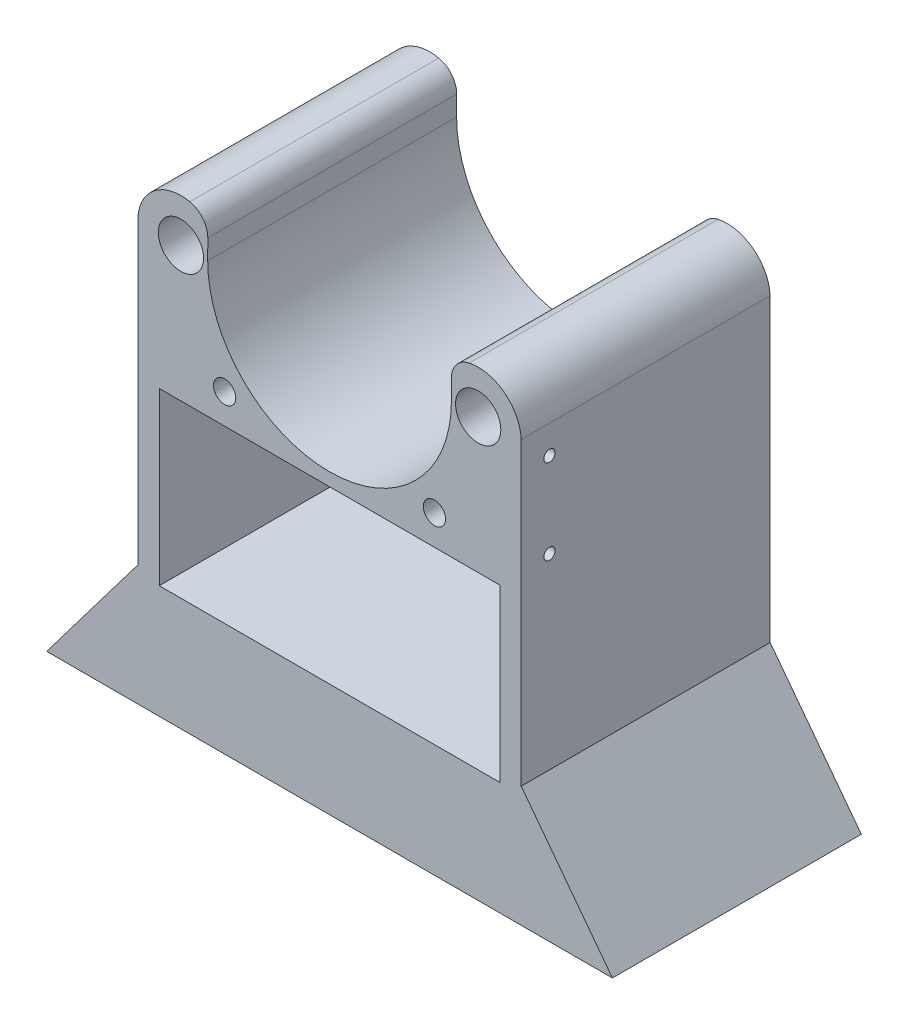
SolidWorks part; units mm, degrees
ref_plane "Front Plane" through (0, 0, 0) normal (0, 0, 1) x (1, 0, 0)
ref_plane "Top Plane" through (0, 0, 0) normal (0, 1, 0) x (1, 0, 0)
ref_plane "Right Plane" through (0, 0, 0) normal (1, 0, 0) x (0, 0, -1)
sketch "Sketch1" plane through (0, 0, 0) normal (0, 0, 1) x (1, 0, 0)
  line L0 (0, 0) -> (0, 54.0315) construction
  line L1 (-38.227, -19.177) -> (38.227, -19.177)
  line L2 (-38.227, -19.177) -> (-38.227, 19.177)
  line L3 (-38.227, 19.177) -> (38.227, 19.177)
  line L4 (38.227, -19.177) -> (38.227, 19.177)
  line L5 (-38.227, -19.177) -> (38.227, 19.177) construction
  line L6 (-38.227, 19.177) -> (38.227, -19.177) construction
  line L7 (0, 54.0315) -> (0, -50.3288) construction
  line L8 (-38.227, 7.4711) -> (-38.227, 58.2157) construction
  line L9 (-43.03, -17.5223) -> (-43.03, 19.177)
  line L10 (-63.5, -44.577) -> (63.5, -44.577)
  line L11 (-43.03, -17.5223) -> (-63.5, -44.577)
  line L12 (-43.03, -17.5223) -> (-43.03, 56.2622) construction
  line L13 (-43.03, 19.177) -> (-43.03, 49.8911)
  line L14 (-23.6995, 49.9018) -> (0, 24.257)
  line L15 (43.03, -17.5223) -> (63.5, -44.577)
  line L16 (43.03, 19.177) -> (43.03, 49.8911)
  line L17 (43.03, -17.5223) -> (43.03, 19.177)
  line L18 (23.6995, 49.9018) -> (0, 24.257)
  circle A0 centre (-33.3645, 49.4395) radius 4.8625
  circle A1 centre (33.3645, 49.4395) radius 4.8625
  arc A2 (-43.03, 49.8911) -> (-23.6995, 49.9018) centre (-33.3645, 49.4395) cw
  arc A3 (43.03, 49.8911) -> (23.6995, 49.9018) centre (33.3645, 49.4395) ccw
  point P0 (0, 0)
  point P11 (-33.3645, 44.577)
  point P14 (-38.227, 49.4395)
  point P24 (0, 24.257)
  dimension "D3" = 9.725
  dimension "D1" = 76.454
  dimension "D2" = 38.354
  dimension "D4" = 0
  dimension "D5" = 25.4
  dimension "D6" = 5.08
  dimension "D7" = 63.5
  dimension "D9" = 25.4
  dimension "D10" = 5.08
extrude "Boss-Extrude1" add sketch "Sketch1" along normal blind 50.8
sketch "Sketch2" plane through (0, 0, 0) normal (0, 0, -1) x (-1, 0, 0)
  line L0 (-43.03, 49.8911) -> (-43.03, -17.5223)
  line L1 (-43.03, -17.5223) -> (-63.5, -44.577)
  line L2 (-63.5, -44.577) -> (63.5, -44.577)
  line L3 (63.5, -44.577) -> (43.03, -17.5223)
  line L4 (43.03, -17.5223) -> (43.03, 49.8911)
  line L5 (23.6995, 49.9018) -> (0, 24.257)
  line L6 (0, 24.257) -> (-23.6995, 49.9018)
  arc A0 (-43.03, 49.8911) -> (-23.6995, 49.9018) centre (-33.3648, 49.8911) cw
  arc A1 (23.6995, 49.9018) -> (43.03, 49.8911) centre (33.3648, 49.8911) cw
extrude "Boss-Extrude2" add sketch "Sketch2" along normal blind 5.08
sketch "Sketch3" plane through (0, 0, -5.08) normal (0, 0, -1) x (-1, 0, 0)
  line L0 (-33.3701, 59.5563) -> (33.3701, 59.5563)
  line L1 (-23.6995, 49.9018) -> (0, 24.257)
  line L2 (0, 24.257) -> (23.6995, 49.9018)
  arc A0 (-23.6995, 49.9018) -> (-43.03, 49.8911) centre (-33.3648, 49.8911) ccw construction
  arc A1 (43.03, 49.8911) -> (23.6995, 49.9018) centre (33.3648, 49.8911) ccw construction
  arc A2 (-33.3701, 59.5563) -> (-23.6995, 49.9018) centre (-33.3701, 49.8857) cw
  arc A3 (23.6995, 49.9018) -> (33.3701, 59.5563) centre (33.3701, 49.8857) cw
extrude "Boss-Extrude3" add sketch "Sketch3" against normal up to surface (55.88 mm away) up to face at (-28.502, 49.4395, 50.8)
sketch "Sketch5" plane through (0, 0, 50.8) normal (0, 0, 1) x (1, 0, 0)
  line L0 (-33.3645, 49.4395) -> (33.3645, 49.4395) construction
  point P4 (0, 49.4395)
ref_axis "Axis1" through (0, 49.4395, 50.8) along (0, 0, -1)
sketch "Sketch6" plane through (0, 0, 50.8) normal (0, 0, 1) x (1, 0, 0)
  line L0 (-24.765, 49.4395) -> (-24.765, 59.5563)
  line L1 (-33.3701, 59.5563) -> (33.3701, 59.5563) construction
  line L2 (24.765, 49.4395) -> (24.765, 59.5563)
  line L3 (-24.765, 59.5563) -> (24.765, 59.5563)
  circle A0 centre (0, 49.4395) radius 24.765
  arc M6 (43.03, 49.8911) -> (23.6995, 49.9018) centre (33.3645, 49.4395) ccw
  arc M7 (23.6995, 49.9018) -> (33.3701, 59.5563) centre (33.3701, 49.8857) cw
  line M8 (33.3701, 59.5563) -> (-33.3701, 59.5563)
  arc M9 (-33.3701, 59.5563) -> (-23.6995, 49.9018) centre (-33.3701, 49.8857) cw
  arc M10 (-23.6995, 49.9018) -> (-43.03, 49.8911) centre (-33.3645, 49.4395) ccw
  dimension "D1" = 49.53
extrude "Cut-Extrude1" cut sketch "Sketch6" against normal blind 157.734 contours A0 L3 M7 M9 M10 M6 | A0 L0 M8 M9 | A0 L2 M7 M8 region at (0, 44.1265, 50.8) region at (-24.0725, 57.4402, 50.8) region at (24.0725, 57.4402, 50.8)
fillet "Fillet1" radius 2.54 2 edges at (24.765, 59.5563, 22.86) (-24.765, 59.5563, 22.86)
sketch "Sketch7" plane through (0, 0, -5.08) normal (0, 0, -1) x (-1, 0, 0)
  circle A0 centre (-23.55, 25.8895) radius 2.5
  circle A1 centre (23.55, 25.8895) radius 2.5
extrude "Cut-Extrude2" cut sketch "Sketch7" against normal blind 157.734
sketch "Sketch8" plane through (0, 0, 0) normal (0, 0, 1) x (1, 0, 0)
  circle A1 centre (18.8761, 0.1739) radius 3.3274
  circle A2 centre (-19.2239, 0.1739) radius 3.3274
extrude "Cut-Extrude3" cut sketch "Sketch8" against normal blind 50.8
sketch "Sketch9" plane through (0, 0, 50.8) normal (0, 0, 1) x (1, 0, 0)
  circle A0 centre (-33.3645, 49.4395) radius 5.08
  circle A1 centre (33.3645, 49.4395) radius 5.08
  dimension "D1" = 10.16
  dimension "D2" = 10.16
extrude "Cut-Extrude4" cut sketch "Sketch9" against normal up to surface (50.8 mm away) up to face at (-28.502, 49.4395, 0)
sketch "Sketch10" plane through (-43.03, 0, 0) normal (-1, 0, 0) x (0, 0, 1)
  line L0 (44.45, 49.8911) -> (44.45, -17.5223) construction
  line L1 (50.8, 49.8911) -> (0, 49.8911) construction
  line L2 (50.8, -17.5223) -> (-5.08, -17.5223) construction
  line L3 (50.8, 49.8911) -> (50.8, -17.5223) construction
  circle A0 centre (44.45, 43.5411) radius 1.27
  circle A1 centre (44.45, 24.4911) radius 1.27
  dimension "D2" = 2.54
  dimension "D3" = 2.54
  dimension "D4" = 6.35
  dimension "D5" = 19.05
  dimension "D1" = 6.35
extrude "Cut-Extrude5" cut sketch "Sketch10" against normal blind 6.35
sketch "Sketch11" plane through (0, 0, -5.08) normal (0, 0, -1) x (-1, 0, 0)
  line L0 (27.3504, 49.4395) -> (27.305, 59.5563)
  line L1 (-27.3504, 49.4395) -> (-27.305, 59.5563)
  circle A0 centre (0, 49.4395) radius 27.3504
  arc A1 (-27.305, 59.5563) -> (-25.5089, 58.8124) centre (-27.305, 57.0163) cw
  arc A2 (-24.765, 57.0163) -> (-27.305, 59.5563) centre (-27.305, 57.0163) ccw construction
  arc A3 (27.305, 59.5563) -> (25.5089, 58.8124) centre (27.305, 57.0163) ccw
  arc A4 (27.305, 59.5563) -> (24.765, 57.0163) centre (27.305, 57.0163) ccw construction
  line M6 (-24.765, 54.2984) -> (-24.765, 57.0163)
  arc M7 (-24.765, 57.0163) -> (-27.305, 59.5563) centre (-27.305, 57.0163) ccw
  arc M17 (27.305, 59.5563) -> (24.765, 57.0163) centre (27.305, 57.0163) ccw
  line M18 (24.765, 57.0163) -> (24.765, 54.2984)
  arc M19 (24.765, 54.2984) -> (23.6995, 49.9018) centre (33.3701, 49.8857) ccw
  arc M20 (23.6995, 49.9018) -> (24.4702, 53.2495) centre (33.3645, 49.4395) cw
  arc M21 (24.4702, 53.2495) -> (-24.4702, 53.2495) centre (0, 49.4395) cw
  arc M22 (-24.4702, 53.2495) -> (-23.6995, 49.9018) centre (-33.3645, 49.4395) cw
  arc M23 (-23.6995, 49.9018) -> (-24.765, 54.2984) centre (-33.3701, 49.8857) ccw
  dimension "D1" = 10.1168
extrude "Cut-Extrude8" cut sketch "Sketch11" against normal blind 60.198 contours A0 M17 M7 M6 M23 M22 M21 M20 M19 M18 | L0 A0 L1 M17 M18 M19 M20 M21 M22 M23 M6 M7 | A0 L1 M7 | A0 L0 M17 region at (0, 22.7487, -5.08) region at (-26.8047, 56.9219, -5.08) region at (0, 51.0402, -5.08) region at (26.8047, 56.9219, -5.08)
sketch "Sketch13" plane through (0, 0, 50.8) normal (0, 0, 1) x (1, 0, 0)
  line L0 (-43.0405, 49.4395) -> (-48.2287, 49.4395)
  line L1 (-27.3165, 56.9924) -> (-24.2675, 60.915)
  circle A0 centre (-33.3645, 49.4395) radius 9.676
  circle A1 centre (-33.3645, 49.4395) radius 14.8642
  arc M2 (-27.3165, 56.9924) -> (-43.03, 49.8911) centre (-33.3645, 49.4395) ccw
  arc M10 (27.3504, 49.4395) -> (-27.3504, 49.4395) centre (0, 49.4395) cw
extrude "Cut-Extrude10" cut sketch "Sketch13" against normal blind 134.112 contours A1 L0 A0 M10 M2 region at (-45.6346, 49.8401, 50.8)
ref_plane "Plane1" through (0, 0, 0) normal (-1, 0, 0) x (0, 0, 1)
mirror "Mirror1" about plane through (0, 0, 0) normal (-1, 0, 0) of "Cut-Extrude10"
mirror "Mirror2" about plane through (0, 0, 0) normal (-1, 0, 0) of "Cut-Extrude5"
fillet "Fillet2" radius 5.08 2 edges at (27.3165, 56.9924, 22.86) (-27.3165, 56.9924, 22.86)
